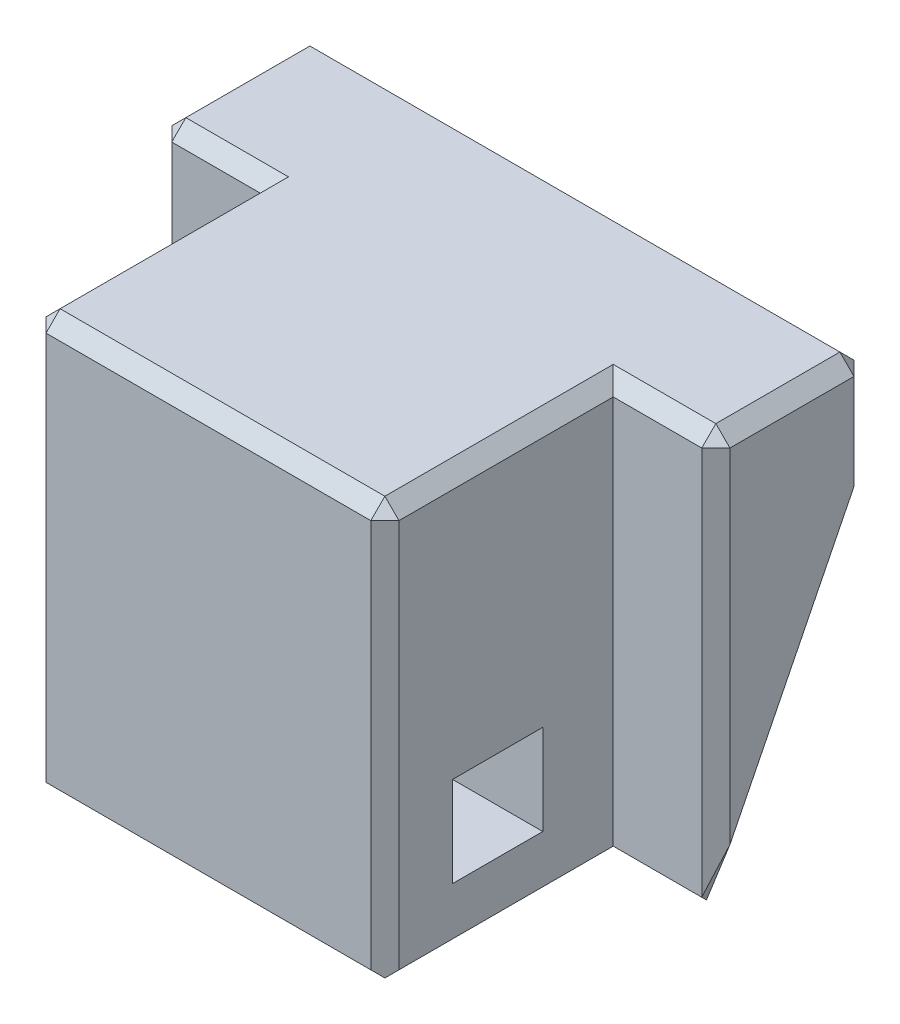
SolidWorks part; units mm, degrees
note: The reader was unsure of these and kept them because the rebuilt part matched: shared geometry of "Sketch4<5>".
ref_plane "Front Plane" through (0, 0, 0) normal (0, 0, 1) x (1, 0, 0)
ref_plane "Top Plane" through (0, 0, 0) normal (0, 1, 0) x (1, 0, 0)
ref_plane "Right Plane" through (0, 0, 0) normal (1, 0, 0) x (0, 0, -1)
ref_plane "Plane1" through (25.9401, 0, 0) normal (1, 0, 0) x (0, 0, -1)
sketch "Sketch4" plane through (25.9401, 0, 0) normal (1, 0, 0) x (0, 0, -1)
  line L1 (-49.5036, 153.574) -> (-25.8261, 153.574) construction
  line L4 (-28.7936, -39.626) -> (-28.7936, -16.6266) construction
  line L9 (-33.5634, -25.0483) -> (-29.0936, -16.1086) construction
  line L15 (-34.7936, 138.574) -> (-42.7936, 138.574) construction
  line L16 (-42.7936, 138.774) -> (-34.6936, 138.774)
  line L17 (-42.7936, -16.426) -> (-42.7936, 143.574) construction
  line L18 (-34.7936, 153.574) -> (-34.7936, 133.574) construction
  line L19 (-34.6936, 138.774) -> (-29.2936, 149.574)
  line L20 (-29.2936, 149.574) -> (-29.2936, 153.574)
  line L22 (-29.2936, 153.574) -> (-42.7936, 153.574)
  line L23 (-42.7936, 153.574) -> (-42.7936, 138.774)
  line L24 (-40.3936, 144.174) -> (-40.3936, 140.974)
  line L25 (-40.3936, 140.974) -> (-37.1936, 140.974)
  line L26 (-37.1936, 140.974) -> (-37.1936, 144.174)
  line L27 (-37.1936, 144.174) -> (-40.3936, 144.174)
  line L28 (-34.6936, 138.774) -> (-34.6936, 153.574)
  dimension "D1" = 0.2
  dimension "D2" = 0.5
  dimension "D3" = 0.1
extrude "Boss-Extrude1" add sketch "Sketch4" along normal offset from surface 0.1 and the other way offset from surface (6.2604 mm away) 0.1 contours L16 L28 L22 L23 L27 L26 L25 L24
extrude "Boss-Extrude2" add sketch "Sketch4<5>" along normal offset from surface 0.1 and the other way offset from surface (9.9 mm away) 0.1 contours L28 L19 L20 L22
sketch "Sketch4<5>" plane through (25.9401, 0, 0) normal (1, 0, 0) x (0, 0, -1) same geometry as "Sketch4"
chamfer "Chamfer1" distance 0.5 angle 45 19 edges at (17.8599, 138.774, 34.6936) (34.0203, 138.774, 34.6936) (32.2005, 153.574, 38.7436) (19.6797, 153.574, 38.7436) (17.8599, 153.574, 34.6936) (16.0401, 153.574, 31.9936) (16.0401, 146.174, 34.6936) (16.0401, 144.174, 31.9936) (16.0401, 151.574, 29.2936) (25.9401, 153.574, 29.2936) (35.8401, 153.574, 31.9936) (35.8401, 151.574, 29.2936) (35.8401, 144.174, 31.9936) (35.8401, 146.174, 34.6936) (34.0203, 153.574, 34.6936) (25.9401, 138.774, 42.7936) (32.2005, 146.174, 42.7936) (19.6797, 146.174, 42.7936) (25.9401, 153.574, 42.7936)
chamfer "Chamfer2" distance 0.5 angle 45 2 edges at (32.2005, 138.774, 38.4936) (19.6797, 138.774, 38.4936)
